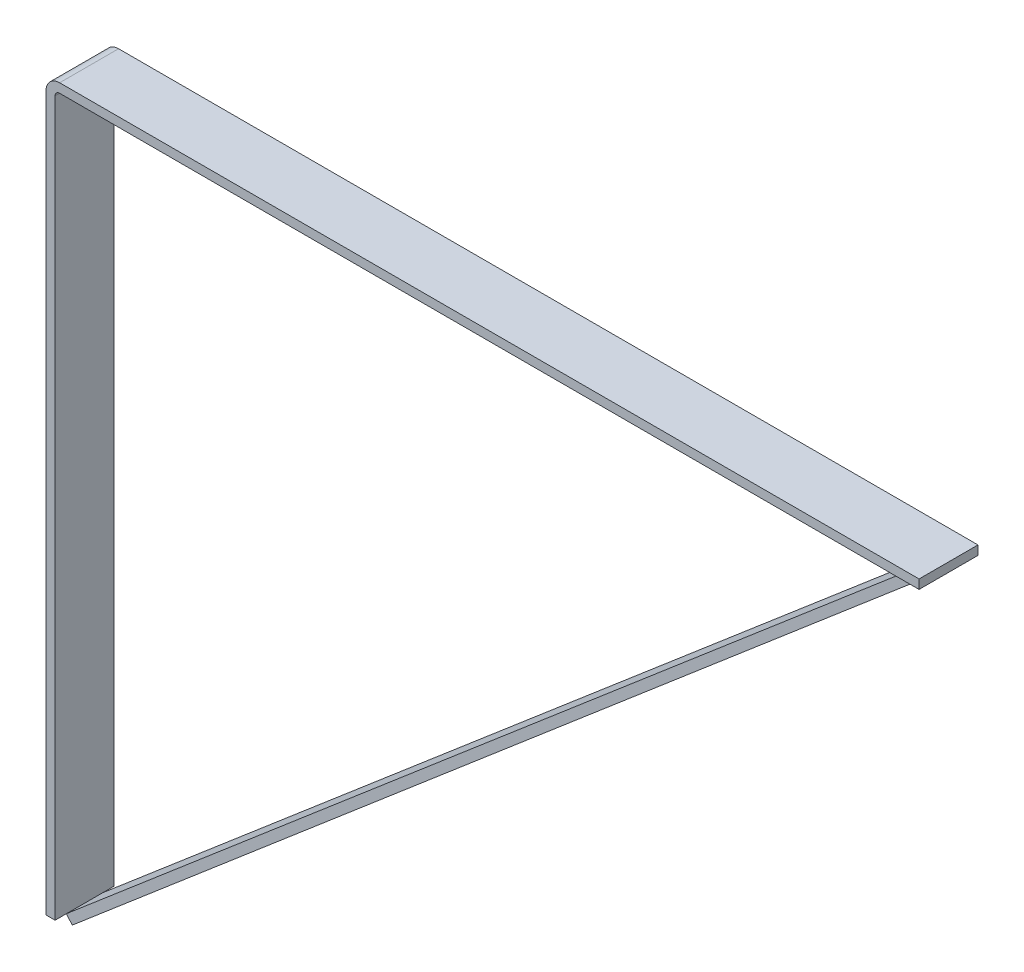
SolidWorks part; units mm, degrees
ref_plane "Front Plane" through (0, 0, 0) normal (0, 0, 1) x (1, 0, 0)
ref_plane "Top Plane" through (0, 0, 0) normal (0, 1, 0) x (1, 0, 0)
ref_plane "Right Plane" through (0, 0, 0) normal (1, 0, 0) x (0, 0, -1)
sketch "Sketch1" plane through (0, 0, 0) normal (0, 0, 1) x (1, 0, 0)
  line L0 (-309.5625, -508) -> (-309.5625, -9.525)
  line L1 (-300.0375, 0) -> (300.0375, 0)
  arc A0 (-309.5625, -9.525) -> (-300.0375, 0) centre (-300.0375, -9.525) cw
  point P6 (-309.5625, 0)
  dimension "D1" = 9.525
  dimension "LG" = 609.6
  dimension "HT" = 508
extrude "Extrude-Thin1" add sketch "Sketch1" along normal mid plane 41.148 thin thin type one direction wall 6.35
sketch "Sketch2" plane through (0, 0, 0) normal (0, 0, 1) x (1, 0, 0)
  line L0 (285.2504, -6.35) -> (-303.2125, -508)
  line L1 (-303.2125, -508) -> (-299.093, -512.8324)
  line L2 (-299.093, -512.8324) -> (295.0386, -6.35)
  line L3 (285.2504, -6.35) -> (295.0386, -6.35)
  line L4 (-300.0375, -6.35) -> (300.0375, -6.35) construction
  dimension "D1" = 6.35
extrude "Boss-Extrude1" add sketch "Sketch2" along normal mid plane 25.4 separate body
